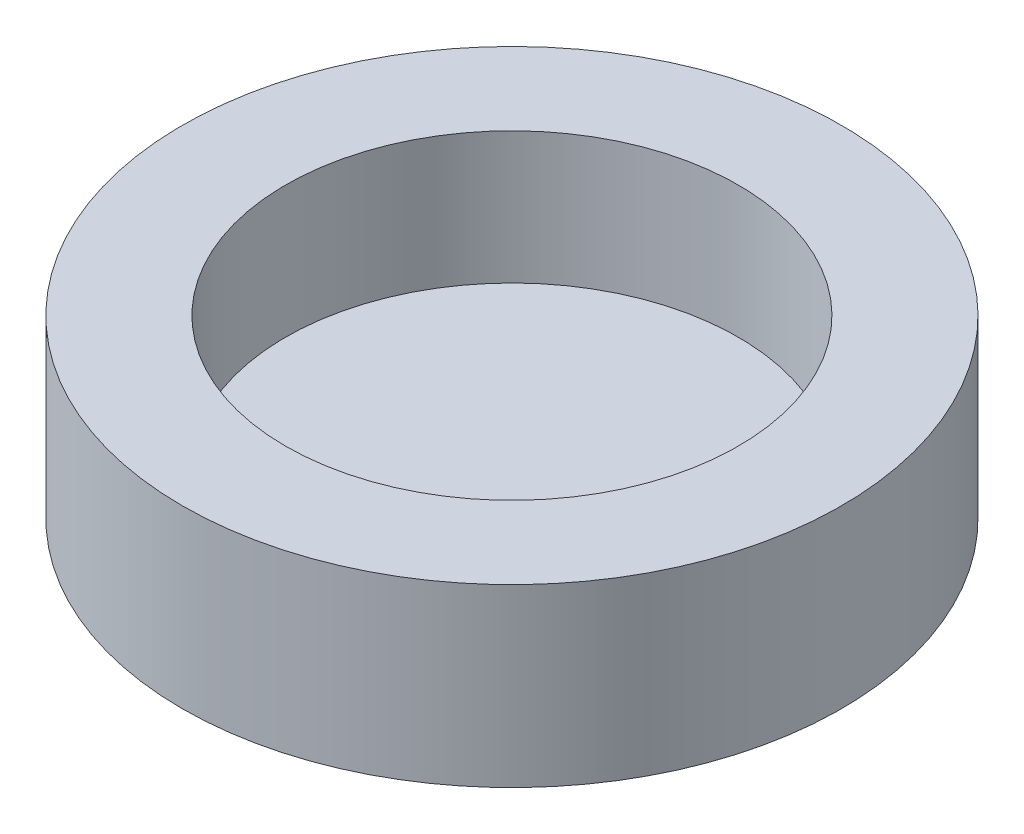
SolidWorks part; units mm, degrees
ref_plane "Front Plane" through (0, 0, 0) normal (0, 0, 1) x (1, 0, 0)
ref_plane "Top Plane" through (0, 0, 0) normal (0, 1, 0) x (1, 0, 0)
ref_plane "Right Plane" through (0, 0, 0) normal (1, 0, 0) x (0, 0, -1)
sketch "Sketch1" plane through (0, 0, 0) normal (0, 1, 0) x (1, 0, 0)
  circle A0 centre (0, 0) radius 7.5
  dimension "D1" = 15
extrude "Boss-Extrude1" add sketch "Sketch1" along normal blind 4
sketch "Sketch2" plane through (0, 4, 0) normal (0, 1, 0) x (1, 0, 0)
  circle A0 centre (0, 0) radius 5.15
  dimension "D1" = 10.3
extrude "Cut-Extrude1" cut sketch "Sketch2" against normal blind 3
